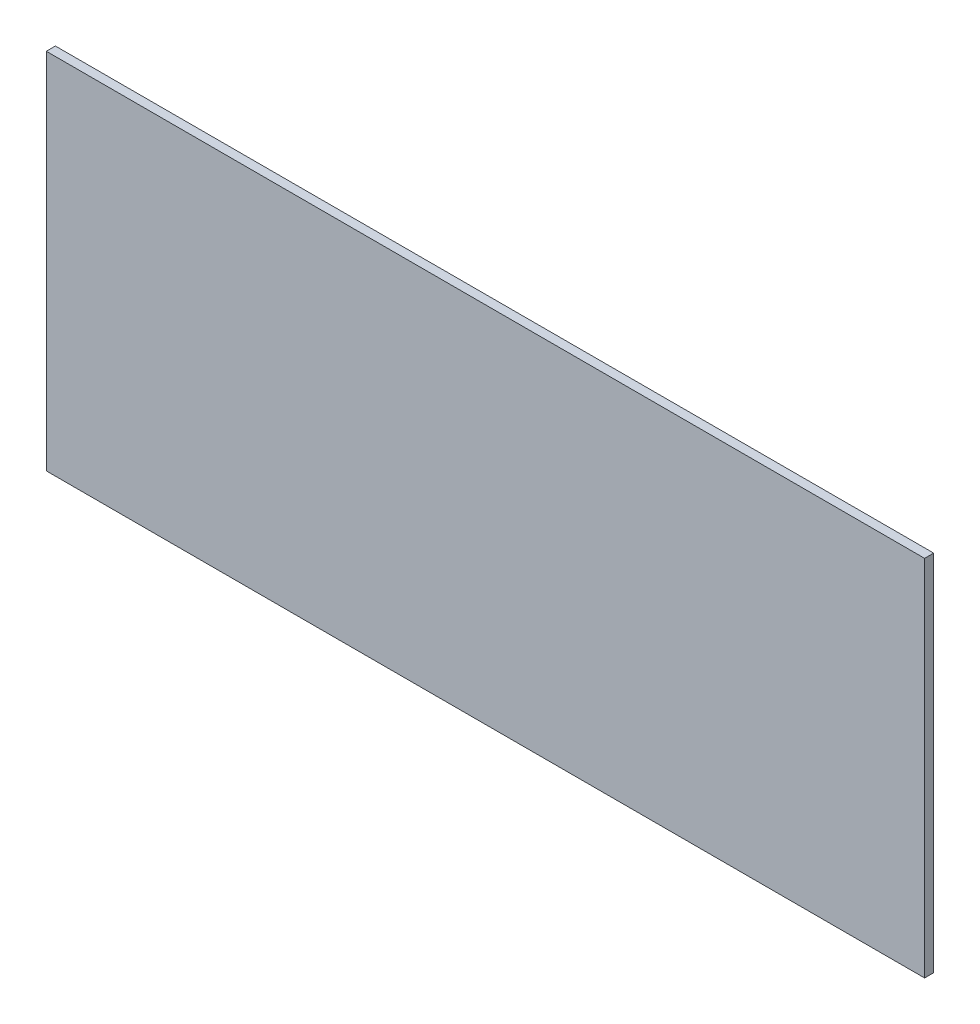
SolidWorks part; units mm, degrees
ref_plane "Front Plane" through (0, 0, 0) normal (0, 0, 1) x (1, 0, 0)
ref_plane "Top Plane" through (0, 0, 0) normal (0, 1, 0) x (1, 0, 0)
ref_plane "Right Plane" through (0, 0, 0) normal (1, 0, 0) x (0, 0, -1)
sketch "Sketch1" plane through (0, 0, 0) normal (0, 0, 1) x (1, 0, 0)
  line L1 (-145, 60) -> (145, 60)
  line L2 (-145, 60) -> (-145, -60)
  line L3 (-145, -60) -> (145, -60)
  line L4 (145, 60) -> (145, -60)
  line L5 (-145, 60) -> (145, -60) construction
  line L6 (-145, -60) -> (145, 60) construction
  point P0 (0, 0)
  dimension "D1" = 120
  dimension "D2" = 290
extrude "Boss-Extrude1" add sketch "Sketch1" along normal blind 3
